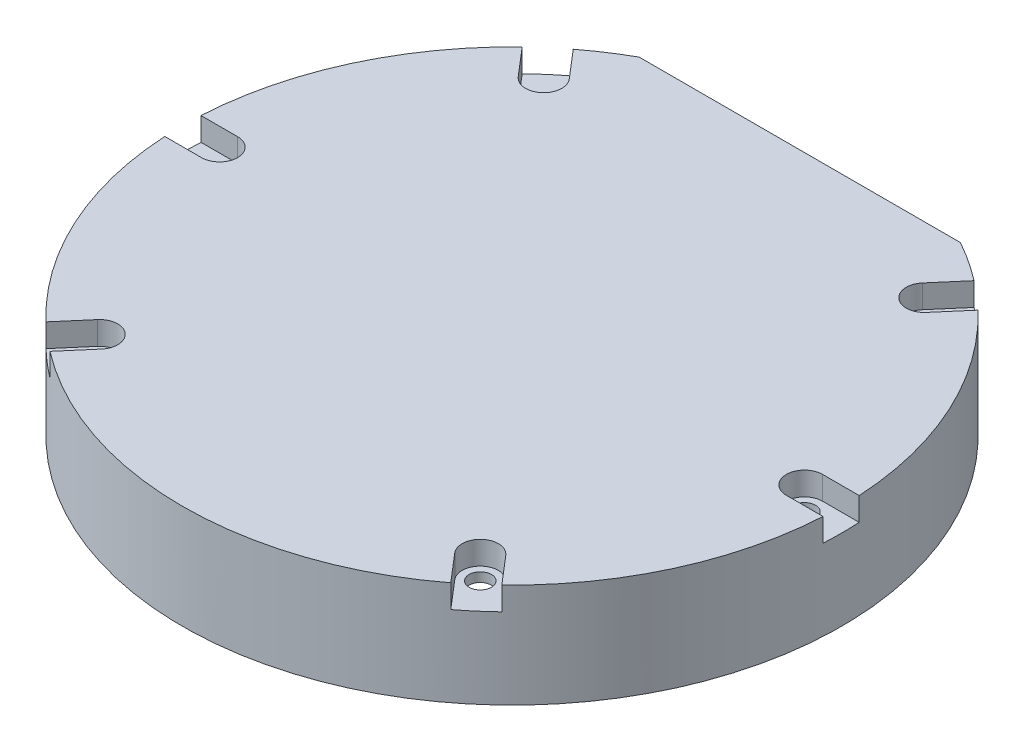
SolidWorks part; units mm, degrees
ref_plane "Front Plane" through (0, 0, 0) normal (0, 0, 1) x (1, 0, 0)
ref_plane "Top Plane" through (0, 0, 0) normal (0, 1, 0) x (1, 0, 0)
ref_plane "Right Plane" through (0, 0, 0) normal (1, 0, 0) x (0, 0, -1)
sketch "Sketch1" plane through (0, 0, 0) normal (0, -1, 0) x (1, 0, 0)
  circle A0 centre (0, 0) radius 35.5
  dimension "D1" = 71
extrude "Boss-Extrude1" add sketch "Sketch1" along normal blind 2
sketch "Sketch2" plane through (0, -2, 0) normal (0, -1, 0) x (1, 0, 0)
  circle A0 centre (0, 0) radius 34
  circle A2 centre (0, 0) radius 35.5 construction
  circle A3 centre (0, 0) radius 35.5
  dimension "D1" = 1.5
extrude "Boss-Extrude2" add sketch "Sketch2" along normal blind 9.2
sketch "Sketch5" plane through (0, -2, 0) normal (0, -1, 0) x (1, 0, 0)
  circle A0 centre (0, 0) radius 34 construction
  circle A1 centre (0, 0) radius 34
  circle A2 centre (0, 0) radius 28.75
  dimension "D1" = 57.5
extrude "Boss-Extrude3" add sketch "Sketch5" along normal blind 1.5
sketch "Sketch3" plane through (0, 0, 0) normal (0, 1, 0) x (1, 0, 0)
  line L0 (-17.2988, 31) -> (17.2988, 31)
  line L1 (0, 42.3765) -> (0, -3.4902) construction
  circle A0 centre (0, 0) radius 35.5 construction
  arc A1 (17.2988, 31) -> (-17.2988, 31) centre (0, 0) ccw
  point P7 (0, -35.5)
  dimension "D1" = 66.5
extrude "Cut-Extrude2" cut sketch "Sketch3" against normal up to next
sketch "Sketch6" plane through (0, -2, 0) normal (0, -1, 0) x (1, 0, 0)
  line L0 (-18.8695, -31) -> (-16, -23.8865)
  line L1 (-16, -23.8865) -> (16, -23.8865)
  line L2 (16, -23.8865) -> (18.8695, -31)
  line L3 (18.8695, -31) -> (-18.8695, -31)
  line L4 (-13.9642, -31) -> (13.9642, -31) construction
  circle A0 centre (0, 0) radius 28.75 construction
  circle A1 centre (0, 0) radius 28.75 construction
  arc A2 (13.9642, -31) -> (-13.9642, -31) centre (0, 0) ccw construction
  point P4 (0, -31)
  point P7 (0, -31)
  point P15 (-18, -28.8444)
  point P17 (18, -28.8444)
  dimension "D1" = 32
  dimension "D2" = 36
extrude "Cut-Extrude3" cut sketch "Sketch6" along normal up to next
sketch "Sketch8" plane through (0, 0, 0) normal (0, 1, 0) x (1, 0, 0)
  line L15 (-31.5, 0) -> (31.5, 0) construction
  line L17 (-20.5, 23.9165) -> (20.5, 23.9165) construction
  line L19 (-20.5, -23.9165) -> (20.5, -23.9165) construction
  circle A1 centre (0, 0) radius 31.5 construction
  point P12 (-20.5, 23.9165)
  point P13 (-31.5, 0)
  point P14 (-20.5, -23.9165)
  point P16 (31.5, 0)
  point P17 (20.5, 23.9165)
  point P52 (20.5, -23.9165)
  dimension "D1" = 63
  dimension "D2" = 41
  dimension "D3" = 41
hole_wizard "M2 Clearance Hole1" positions "Sketch8" profile "Sketch9" hole size "M2" standard "DIN" end condition up to next
sketch "Sketch9" plane through (-20.5, 0, -23.9165) normal (1, 0, 0) x (0, 0, 1)
  line L0 (0, 0) -> (0, 3.5)
  line L1 (0, 3.5) -> (1.2, 3.5)
  line L2 (1.2, 3.5) -> (1.2, 0)
  line L5 (1.2, 0) -> (0, 0)
  line L11 (0, -6.35) -> (0, 107.95) construction
  dimension "Thru Hole Dia." = 2.4
  dimension "Thru Hole Depth" = 3.5
sketch "Sketch10" plane through (0, 0, 0) normal (0, 1, 0) x (1, 0, 0)
  line L0 (-35.4464, 1.95) -> (-31.5, 1.95)
  line L1 (-35.4464, -1.95) -> (-31.5, -1.95)
  line L2 (-24.5488, 25.6438) -> (-21.9805, 22.6475)
  line L3 (-21.5877, 28.1819) -> (-19.0195, 25.1856)
  line L4 (-21.5877, -28.1819) -> (-19.0195, -25.1856)
  line L5 (-24.5488, -25.6438) -> (-21.9805, -22.6475)
  line L6 (0, 40.747) -> (0, -49959.253) construction
  line L7 (24.5488, -25.6438) -> (21.9805, -22.6475)
  line L8 (21.5877, -28.1819) -> (19.0195, -25.1856)
  line L9 (21.5877, 28.1819) -> (19.0195, 25.1856)
  line L10 (24.5488, 25.6438) -> (21.9805, 22.6475)
  line L11 (35.4464, -1.95) -> (31.5, -1.95)
  line L12 (35.4464, 1.95) -> (31.5, 1.95)
  arc A0 (-17.2988, 31) -> (17.2988, 31) centre (0, 0) ccw construction
  arc A1 (-21.5877, 28.1819) -> (-24.5488, 25.6438) centre (0, 0) ccw
  arc A2 (-31.5, 1.95) -> (-31.5, -1.95) centre (-31.5, 0) cw
  circle A3 centre (-31.5, 0) radius 1.2 construction
  circle A4 centre (-31.5, 0) radius 1.2
  arc A5 (-21.9805, 22.6475) -> (-19.0195, 25.1856) centre (-20.5, 23.9165) ccw
  circle A6 centre (-20.5, 23.9165) radius 1.2 construction
  circle A7 centre (-20.5, 23.9165) radius 1.2
  arc A8 (-21.9805, -22.6475) -> (-19.0195, -25.1856) centre (-20.5, -23.9165) cw
  circle A9 centre (-20.5, -23.9165) radius 1.2 construction
  circle A10 centre (-20.5, -23.9165) radius 1.2
  circle A11 centre (20.5, -23.9165) radius 1.2
  arc A12 (21.9805, -22.6475) -> (19.0195, -25.1856) centre (20.5, -23.9165) ccw
  circle A13 centre (20.5, 23.9165) radius 1.2
  arc A14 (21.9805, 22.6475) -> (19.0195, 25.1856) centre (20.5, 23.9165) cw
  circle A15 centre (31.5, 0) radius 1.2
  arc A16 (31.5, 1.95) -> (31.5, -1.95) centre (31.5, 0) ccw
  arc A17 (-35.4464, 1.95) -> (-35.4464, -1.95) centre (0, 0) ccw
  arc A18 (-24.5488, -25.6438) -> (-21.5877, -28.1819) centre (0, 0) ccw
  arc A19 (21.5877, -28.1819) -> (24.5488, -25.6438) centre (0, 0) ccw
  arc A20 (35.4464, -1.95) -> (35.4464, 1.95) centre (0, 0) ccw
  arc A21 (24.5488, 25.6438) -> (21.5877, 28.1819) centre (0, 0) ccw
  dimension "D1" = 3.9
extrude "Cut-Extrude4" cut sketch "Sketch10" against normal blind 2.5
